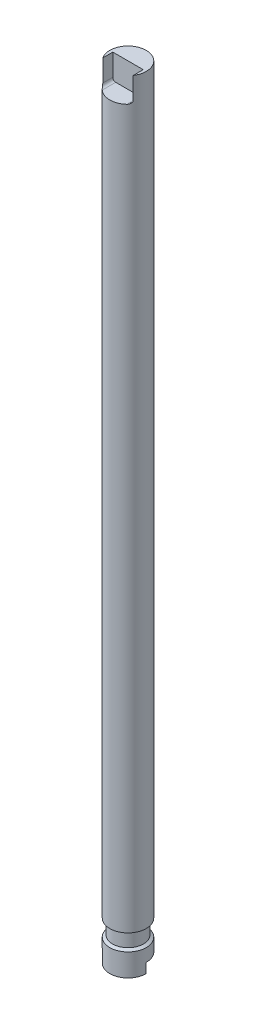
SolidWorks part; units mm, degrees
material "Литая легированная сталь"
ref_plane "Спереди" through (0, 0, 0) normal (0, 0, 1) x (1, 0, 0)
ref_plane "Сверху" through (0, 0, 0) normal (0, 1, 0) x (1, 0, 0)
ref_plane "Справа" through (0, 0, 0) normal (1, 0, 0) x (0, 0, -1)
sketch "Эскиз2" plane through (0, 0, 0) normal (0, 1, 0) x (1, 0, 0)
  circle A0 centre (0, 0) radius 2.8
extrude "Вытянуть1" add sketch "Эскиз2" along normal blind 120
sketch "Эскиз3" plane through (0, 0, 0) normal (0, 0, 1) x (1, 0, 0)
  line L0 (2.8, 0) -> (2.8, 120) construction
  line L1 (-2.8, 0) -> (2.8, 0)
  line L2 (-2.8, 0) -> (-2.8, 1.5)
  line L3 (-2.8, 1.5) -> (2.8, 1.5)
  line L4 (2.8, 0) -> (2.8, 1.5)
extrude "Вытянуть2" cut sketch "Эскиз3" against normal through all
sketch "Эскиз5" plane through (0, 0, 0) normal (0, 0, 1) x (1, 0, 0)
  line L0 (-2.376, 5.7316) -> (-2.8, 5.9966)
  line L1 (-2.8, 3.4667) -> (-2.376, 3.7316)
  line L2 (-2.8, 120) -> (-2.8, 1.5) construction
  line L3 (-2.376, 3.7316) -> (-2.376, 5.7316)
  line L4 (-2.8, 5.9966) -> (-2.8, 3.4667)
  line L5 (0, 0) -> (0, 8.8041) construction
revolve "Вырез-Повернуть1" cut sketch "Эскиз5" angle 360 about L5
sketch "Эскиз6" plane through (0, 0, 0) normal (0, 0, 1) x (1, 0, 0)
  line L0 (-2.3378, 120.3513) -> (-2.3378, 116.6451)
  line L2 (-2.3378, 120.3513) -> (2.3378, 120.3513)
  line L4 (2.3378, 120.3513) -> (2.3378, 116.6451)
  line L6 (-1.8934, 116.2007) -> (1.8934, 116.2007)
  arc A0 (-2.3378, 116.6451) -> (-1.8934, 116.2007) centre (-1.8934, 116.6451) ccw
  arc A1 (2.3378, 116.6451) -> (1.8934, 116.2007) centre (1.8934, 116.6451) cw
extrude "Вытянуть6" cut sketch "Эскиз6" along normal through all and the other way blind 0.0001
scale "Масштаб1" scale about centroid uniform scaling yes scale factor 10
